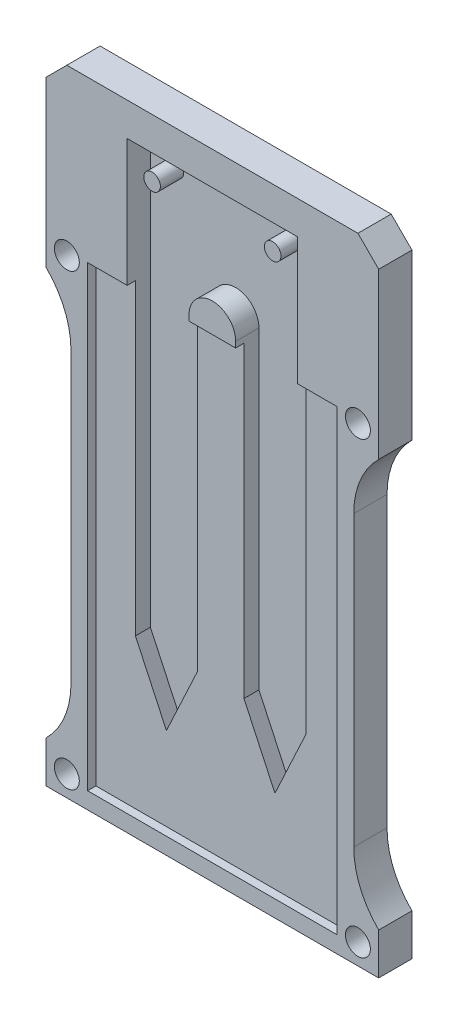
SolidWorks part; units mm, degrees
ref_plane "Alzado" through (0, 0, 0) normal (1, 0, 0) x (0, 1, 0)
ref_plane "Planta" through (0, 0, 0) normal (0, 0, 1) x (0, 1, 0)
ref_plane "Vista lateral" through (0, 0, 0) normal (0, 1, 0) x (-1, 0, 0)
sketch "Croquis2" plane through (0, 0, 0) normal (0, 0, 1) x (0, 1, 0)
  line L0 (-24.5, 20) -> (-24.5, 17)
  line L1 (-29.5, -20) -> (-24.5, -20)
  line L2 (-29.5, -20) -> (-29.5, 20)
  line L3 (-29.5, 20) -> (-24.5, 20)
  line L4 (29.5, -20) -> (29.5, -10.25)
  line L5 (-29.5, -20) -> (29.5, 20) construction
  line L6 (-29.5, 20) -> (29.5, -20) construction
  line L7 (-24.5, 17) -> (24.5, 17)
  line L8 (24.5, 17) -> (24.5, 20)
  line L9 (-24.5, -20) -> (-24.5, -17)
  line L10 (-24.5, -17) -> (24.5, -17)
  line L11 (24.5, -17) -> (24.5, -20)
  line L12 (24.5, 20) -> (29.5, 20)
  line L13 (24.5, -20) -> (29.5, -20)
  line L14 (29.5, -15) -> (42.8, -15)
  line L15 (-27.5, -15) -> (27.5, -15)
  line L16 (-27.5, -15) -> (-27.5, 15)
  line L17 (-27.5, 15) -> (27.5, 15)
  line L18 (27.5, -15) -> (27.5, 15)
  line L19 (-27.5, -15) -> (27.5, 15) construction
  line L20 (-27.5, 15) -> (27.5, -15) construction
  line L21 (42.8, -10.25) -> (42.8, 10.25)
  line L22 (42.8, 15) -> (29.5, 15)
  line L23 (-17.5, -15) -> (-17.5, 15)
  line L24 (29.5, -20) -> (46.8, -20)
  line L25 (46.8, -20) -> (46.8, 20)
  line L26 (46.8, 20) -> (29.5, 20)
  line L27 (42.8, 10.25) -> (-9.5, 10.25)
  line L28 (42.8, -10.25) -> (-9.5, -10.25)
  line L29 (0, 0) -> (-17.5, 0) construction
  line L31 (28.2, 2.8) -> (-9.5, 2.8)
  line L32 (28.2, -2.8) -> (-9.5, -2.8)
  line L33 (-9.5, 2.8) -> (-17.5, 6.525)
  line L34 (42.8, 10.25) -> (42.8, 15)
  line L35 (42.8, -10.25) -> (42.8, -15)
  line L36 (-17.5, 6.525) -> (-9.5, 10.25)
  line L37 (-9.5, -2.8) -> (-17.5, -6.525)
  line L38 (-17.5, -6.525) -> (-9.5, -10.25)
  line L39 (29.5, 10.25) -> (29.5, 20)
  circle A0 centre (27, 17.5) radius 1.5
  circle A2 centre (-27, -17.5) radius 1.5
  circle A3 centre (-27, 17.5) radius 1.5
  circle A4 centre (27, -17.5) radius 1.5
  arc A5 (28.2, 2.8) -> (28.2, -2.8) centre (28.2, 0) cw
  circle A9 centre (39.8, 7.25) radius 1
  circle A10 centre (39.8, -7.25) radius 1
  point P0 (0, 0)
  point P14 (0, 0)
  point P19 (-24.5, 18.5)
  point P20 (-27, 17.5)
  point P21 (27, 17.5)
  point P22 (27, -17.5)
  point P23 (-27, -17.5)
  point P42 (27.5, -10.25)
  point P52 (31, 0)
  point P63 (-17.5, 6.525)
  point P72 (27.5, 10.25)
  dimension "D10" = 3
  dimension "D20" = 2
  dimension "D16" = 2.8
  dimension "D1" = 59
  dimension "D2" = 40
  dimension "D5" = 30
  dimension "D3" = 2
  dimension "D4" = 5
  dimension "D6" = 2.5
  dimension "D8" = 2.5
  dimension "D9" = 2.5
  dimension "D11" = 55
  dimension "D7" = 2.5
  dimension "D13" = 10
  dimension "D12" = 60.3
  dimension "D15" = 20.5
  dimension "D17" = 5.6
  dimension "D21" = 3
  dimension "D22" = 3
  dimension "D23" = 3
  dimension "D14" = 4
  dimension "D24" = 7.45
  dimension "D25" = 3.725
  dimension "D26" = 8
  dimension "D18" = 48.5
extrude "Saliente-Extruir4" add sketch "Croquis2" along normal blind 4 contours L4 L28 L18 L15 L16 L17 L27 L12 L8 L7 L0 L3 L2 L1 L9 L10 L11 L13 A4 A3 A2 A0 | L21 L35 L14 L4 L24 L25 L26 L22 L34 | L28 L4 L14 L35 | L27 L34 L22 L4 | A5 L18 | A9 | A10 region at (-18.5, -25.2128, 0) region at (-19.5642, 38.15, 0) region at (-12.625, 36.15, 0) region at (12.625, 36.15, 0) region at (0, 29.0169, 0) region at (-7.25, 39.8, 0) region at (7.25, 39.8, 0)
extrude "Saliente-Extruir5" add sketch "Croquis2<7>" along normal blind 3 contours L15 L23 L17 L16 | L27 L18 L17 L23 | L32 L18 L31 L23 | L18 L28 L23 L15 region at (-12.3893, 3.7076, 0) region at (0, 2.9026, 0) region at (0, -22.5, 0) region at (12.3893, 3.7076, 0)
sketch "Croquis2<7>" plane through (0, 0, 0) normal (0, 0, 1) x (0, 1, 0) same geometry as "Croquis2"
extrude "Saliente-Extruir6" add sketch "Croquis2<8>" along normal blind 1.2 contours L37 L38 L28 L18 L32 | L36 L33 L31 L18 L27 | L18 A5 L28 L21 L27 A10 A9 region at (0, 35.3917, 0) region at (-6.525, 6.935, 0) region at (6.525, 6.935, 0)
sketch "Croquis2<8>" plane through (0, 0, 0) normal (0, 0, 1) x (0, 1, 0) same geometry as "Croquis2"
fillet "Redondeo2" radius 10 4 edges at (17, -24.5, 2) (17, 24.5, 2) (-17, -24.5, 2) (-17, 24.5, 2)
chamfer "Chaflán2" distance 2.5 angle 45 2 edges at (-20, 46.8, 2) (20, 46.8, 2)
equation "\"D25@Croquis2\"=\"D24@Croquis2\"/2"
